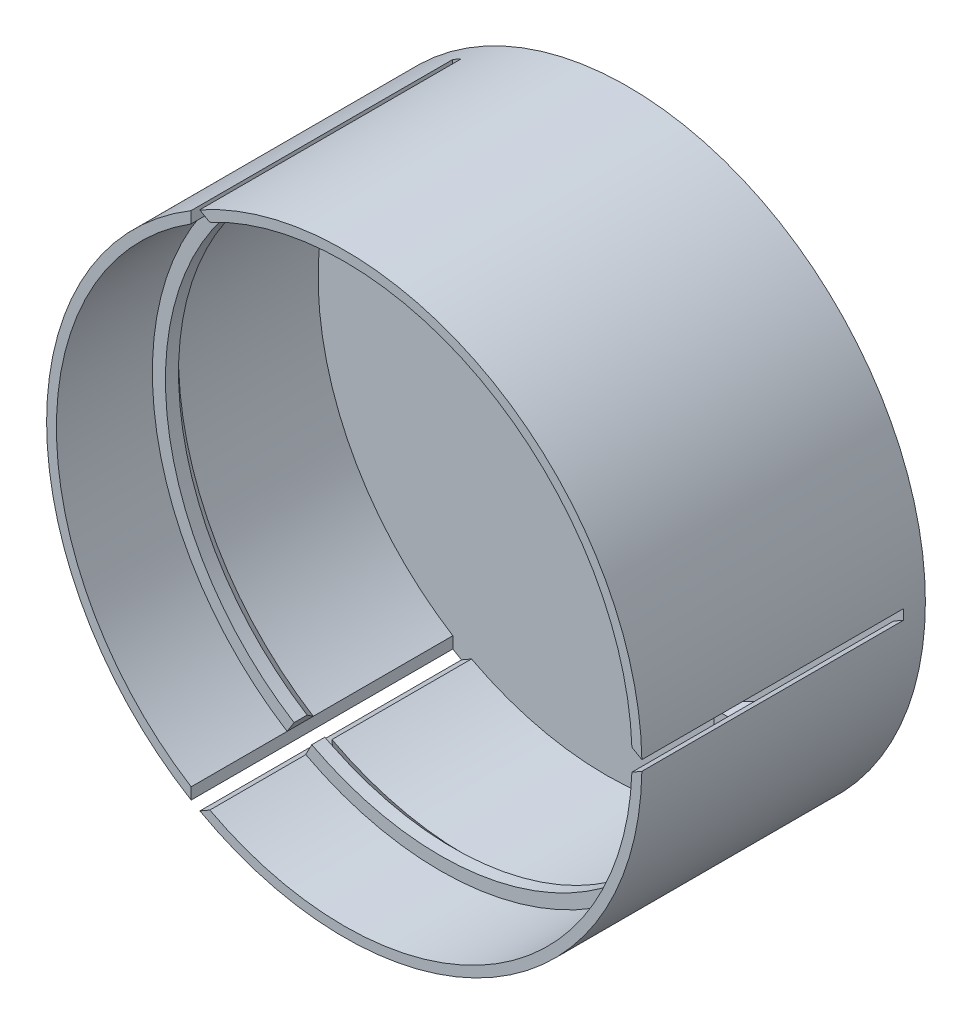
SolidWorks part; units mm, degrees
ref_plane "Front" through (0, 0, 0) normal (0, 0, 1) x (1, 0, 0)
ref_plane "Top" through (0, 0, 0) normal (0, 1, 0) x (1, 0, 0)
ref_plane "Right" through (0, 0, 0) normal (1, 0, 0) x (0, 0, -1)
sketch "Sketch1" plane through (0, 0, 0) normal (0, 0, 1) x (1, 0, 0)
  circle A0 centre (0, 0) radius 68.25
  dimension "D1" = 136.5
extrude "Boss-Extrude2" add sketch "Sketch1" along normal blind 55 and the other way blind 10
sketch "Sketch3" plane through (0, 0, 55) normal (0, 0, 1) x (1, 0, 0)
  line L0 (-30.8483, 58.3471) -> (-35.1322, 60.8191)
  line L1 (70.237, 0.0159) -> (65.9531, 2.4879)
  line L2 (-35.1322, 60.8191) -> (-35.1311, 55.8731)
  line L3 (-35.1048, -60.835) -> (-30.822, -58.361)
  line L4 (-35.1059, -55.889) -> (-35.1048, -60.835)
  line L5 (65.9542, -2.4581) -> (70.237, 0.0159)
  arc A0 (-35.1311, 55.8731) -> (-35.1059, -55.889) centre (0, 0) ccw
  arc A1 (65.9531, 2.4879) -> (-30.8483, 58.3471) centre (0, 0) ccw
  arc A2 (-30.822, -58.361) -> (65.9542, -2.4581) centre (0, 0) ccw
  point P3 (-35.2377, 61.0495)
  dimension "D1" = 132
extrude "Cut-Extrude1" cut sketch "Sketch3" against normal blind 60
ref_plane "Notch Plane" through (0, 0, 30) normal (0, 0, 1) x (1, 0, 0)
sketch "Sketch4" plane through (0, 0, 30) normal (0, 0, 1) x (1, 0, 0)
  line L0 (-35.1311, 55.8731) -> (-33.5343, 53.3334)
  line L1 (-30.8483, 58.3471) -> (-29.4461, 55.6949)
  line L2 (65.9531, 2.4879) -> (62.9509, 2.4879)
  line L3 (65.9542, -2.4581) -> (62.952, -2.4581)
  line L4 (-30.8483, -58.3471) -> (-29.4461, -55.6949)
  line L5 (-35.1059, -55.889) -> (-33.5102, -53.3486)
  arc A0 (-30.8483, -58.3471) -> (65.9542, -2.4581) centre (0, 0) ccw
  arc A1 (-29.4461, -55.6949) -> (62.952, -2.4581) centre (0, 0) ccw
  circle A2 centre (0, 0) radius 63 construction
  circle A3 centre (0, 0) radius 66 construction
  arc A4 (-33.5343, 53.3334) -> (-33.5102, -53.3486) centre (0, 0) ccw
  arc A5 (-35.1311, 55.8731) -> (-35.1059, -55.889) centre (0, 0) ccw
  arc A6 (62.9509, 2.4879) -> (-29.4461, 55.6949) centre (0, 0) ccw
  arc A7 (65.9531, 2.4879) -> (-30.8483, 58.3471) centre (0, 0) ccw
  dimension "D1" = 3
extrude "Boss-Extrude3" add sketch "Sketch4" along normal blind 3
fillet "Fillet1" radius 3 3 edges at (33.0129, -57.1502, 30) (32.9871, 57.1651, 30) (-66, -0.0149, 30) profile chamfer
